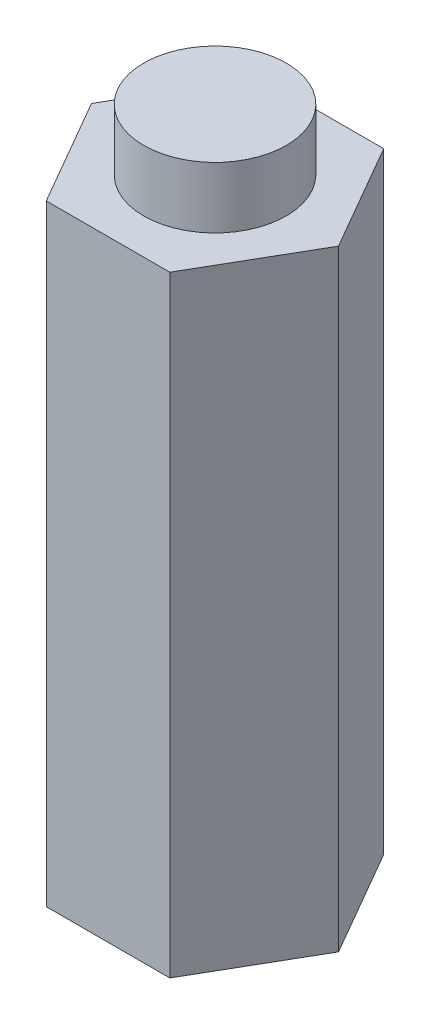
SolidWorks part; units mm, degrees
ref_plane "Front Plane" through (0, 0, 0) normal (0, 0, 1) x (1, 0, 0)
ref_plane "Top Plane" through (0, 0, 0) normal (0, 1, 0) x (1, 0, 0)
ref_plane "Right Plane" through (0, 0, 0) normal (1, 0, 0) x (0, 0, -1)
sketch "Sketch1" plane through (0, 0, 0) normal (0, 1, 0) x (1, 0, 0)
  line L0 (-55, 0) -> (55, 0) construction
  line L1 (12.1244, 0) -> (6.0622, 10.5)
  line L2 (6.0622, 10.5) -> (-6.0622, 10.5)
  line L3 (-6.0622, 10.5) -> (-12.1244, 0)
  line L4 (-12.1244, 0) -> (-6.0622, -10.5)
  line L5 (-6.0622, -10.5) -> (6.0622, -10.5)
  line L6 (6.0622, -10.5) -> (12.1244, 0)
  circle A0 centre (0, 0) radius 10.5 construction
  circle A1 centre (0, 0) radius 7
  dimension "D1" = 21
  dimension "D2" = 14
extrude "Boss-Extrude1" add sketch "Sketch1" along normal blind 60 contours A1 | L5 L6 L1 L2 L3 L4 A1 region at (8.8155, 0, 5.0896) region at (0, 0, 0)
extrude "Boss-Extrude2" add sketch "Sketch1<3>" along normal blind 66 contours A1 region at (0, 0, 0)
sketch "Sketch1<3>" plane through (0, 0, 0) normal (0, 1, 0) x (1, 0, 0) same geometry as "Sketch1"
